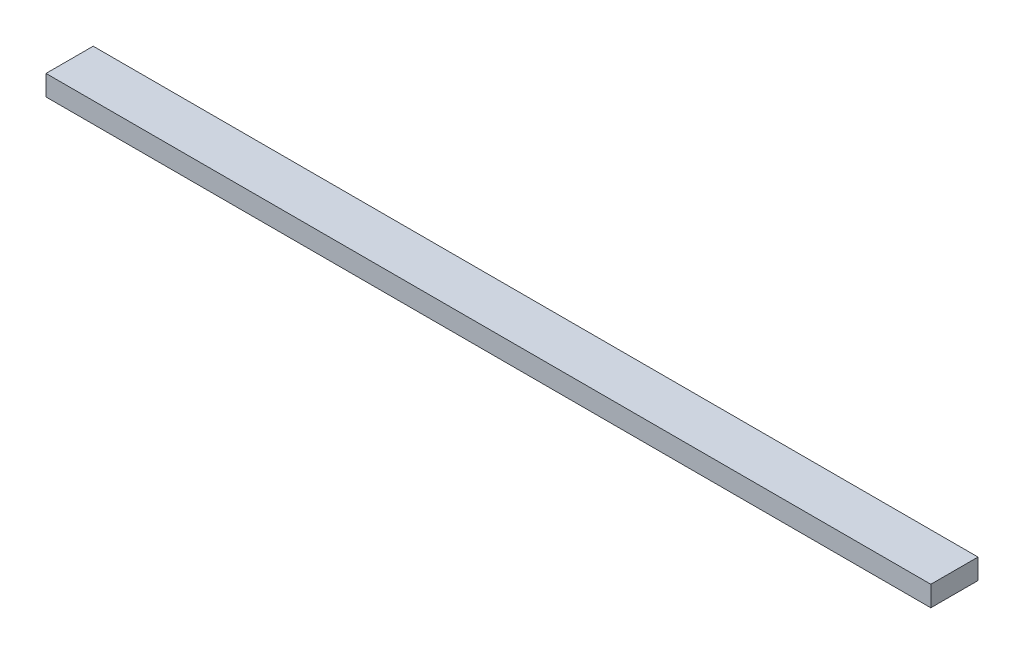
SolidWorks part; units mm, degrees
material "Pine"
ref_plane "Front Plane" through (0, 0, 0) normal (0, 0, 1) x (1, 0, 0)
ref_plane "Top Plane" through (0, 0, 0) normal (0, 1, 0) x (1, 0, 0)
ref_plane "Right Plane" through (0, 0, 0) normal (1, 0, 0) x (0, 0, -1)
sketch "Sketch1" plane through (0, 0, 0) normal (1, 0, 0) x (0, 0, -1)
  line L1 (44.0531, -19.05) -> (-44.0531, -19.05)
  line L2 (44.0531, -19.05) -> (44.0531, 19.05)
  line L3 (44.0531, 19.05) -> (-44.0531, 19.05)
  line L4 (-44.0531, -19.05) -> (-44.0531, 19.05)
  line L5 (44.0531, -19.05) -> (-44.0531, 19.05) construction
  line L6 (44.0531, 19.05) -> (-44.0531, -19.05) construction
  point P0 (0, 0)
  dimension "D1" = 88.1063
  dimension "D2" = 38.1
extrude "Boss-Extrude1" add sketch "Sketch1" along normal up to surface (1652.5875 mm away)
